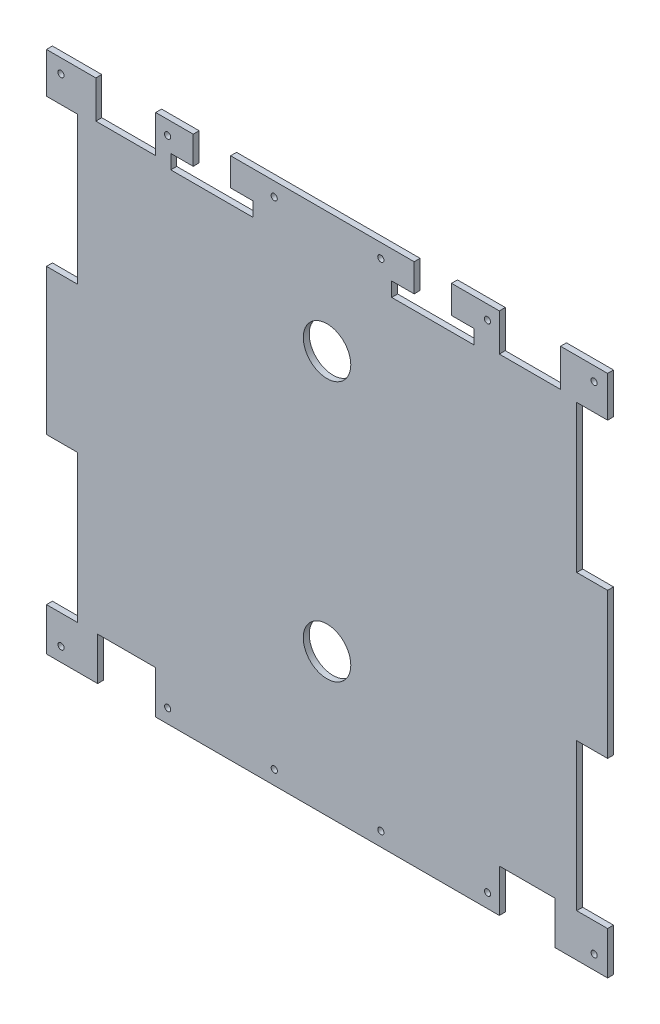
SolidWorks part; units mm, degrees
material "PBT General Purpose"
ref_plane "Front" through (0, 0, 0) normal (0, 0, 1) x (1, 0, 0)
ref_plane "Top" through (0, 0, 0) normal (0, 1, 0) x (1, 0, 0)
ref_plane "Right" through (0, 0, 0) normal (1, 0, 0) x (0, 0, -1)
sketch "Sketch5" plane through (0, 0, 0) normal (0, 0, 1) x (1, 0, 0)
  line L0 (47.1246, -7.4523) -> (30.6146, -7.4523)
  line L1 (-252.8494, 249.5587) -> (-226.474, 249.5587)
  line L2 (-252.8494, 249.5587) -> (-252.8494, 227.8859)
  line L3 (-252.8494, -30.3493) -> (-225.4703, -30.3493)
  line L4 (47.1246, 249.5587) -> (47.1246, 227.8859)
  line L5 (30.6146, -7.4523) -> (30.6146, 71.2877)
  line L6 (30.6146, 71.2877) -> (47.1246, 71.2877)
  line L8 (47.1246, -7.4523) -> (47.1246, -30.3493)
  line L9 (47.1246, 149.1459) -> (30.6146, 149.1459)
  line L10 (30.6146, 149.1459) -> (30.6146, 227.8859)
  line L11 (30.6146, 227.8859) -> (47.1246, 227.8859)
  line L13 (47.1246, 149.1459) -> (47.1246, 71.2877)
  line L14 (-252.8494, 227.8859) -> (-236.3394, 227.8859)
  line L15 (-236.3394, 227.8859) -> (-236.3394, 149.1459)
  line L16 (-236.3394, 149.1459) -> (-252.8494, 149.1459)
  line L18 (-252.8494, 149.1459) -> (-252.8494, 71.2877)
  line L19 (-252.8494, 71.2877) -> (-236.3394, 71.2877)
  line L20 (-236.3394, 71.2877) -> (-236.3394, -7.4523)
  line L21 (-236.3394, -7.4523) -> (-252.8494, -7.4523)
  line L23 (-252.8494, -7.4523) -> (-252.8494, -30.3493)
  line L24 (47.1246, -22.8907) -> (-72.4065, -22.8907) construction
  line L25 (-252.8494, 242.1016) -> (-174.4024, 242.1016) construction
  line L26 (-75.7065, -22.8907) -> (-252.8494, -22.8907) construction
  line L27 (-56.3024, 249.5587) -> (-56.3024, 234.6507)
  line L28 (-56.3024, 227.0307) -> (-36.3024, 227.0307)
  line L29 (-36.3024, 234.6507) -> (-36.3024, 249.5587)
  line L31 (-174.4024, 249.5587) -> (-174.4024, 234.6507)
  line L32 (-174.4024, 227.0307) -> (-154.4024, 227.0307)
  line L33 (-154.4024, 234.6507) -> (-154.4024, 249.5587)
  line L35 (-154.4024, 249.5587) -> (-56.3024, 249.5587)
  line L36 (-154.4024, 242.1016) -> (-56.3024, 242.1016) construction
  line L37 (-36.3024, 249.5587) -> (-10.756, 249.5587)
  line L38 (-36.3024, 242.1016) -> (47.1246, 242.1016) construction
  line L39 (-36.3024, 234.6507) -> (-24.3024, 234.6507)
  line L40 (-252.8494, 234.6507) -> (47.1506, 234.6507) construction
  line L41 (-24.3024, 234.6507) -> (-24.3024, 227.0307)
  line L42 (-24.3024, 227.0307) -> (-36.3024, 227.0307)
  line L43 (-56.3024, 234.6507) -> (-68.3024, 234.6507)
  line L44 (-174.4024, 234.6507) -> (-186.4024, 234.6507)
  line L45 (-54.6336, 234.6507) -> (-154.6336, 234.6507) construction
  line L46 (-68.3024, 234.6507) -> (-68.3024, 227.0307)
  line L47 (-68.3024, 227.0307) -> (-56.3024, 227.0307)
  line L48 (-186.4024, 234.6507) -> (-186.4024, 227.0307)
  line L49 (-186.4024, 227.0307) -> (-174.4024, 227.0307)
  line L50 (-154.4024, 234.6507) -> (-142.4024, 234.6507)
  line L51 (-142.4024, 234.6507) -> (-142.4024, 227.0307)
  line L52 (-142.4024, 227.0307) -> (-154.4024, 227.0307)
  line L53 (-194.456, 249.5587) -> (-174.4024, 249.5587)
  line L55 (-10.756, 249.5587) -> (-10.756, 229.5587)
  line L56 (-10.756, 229.5587) -> (21.9637, 229.5587)
  line L57 (21.9637, 249.5587) -> (21.9637, 229.5587)
  line L59 (-226.474, 249.5587) -> (-226.474, 229.5587)
  line L60 (-226.474, 229.5587) -> (-194.456, 229.5587)
  line L61 (-194.456, 249.5587) -> (-194.456, 229.5587)
  line L62 (21.9637, 249.5587) -> (47.1246, 249.5587)
  line L63 (-194.456, -30.3493) -> (-10.756, -30.3493)
  line L64 (-225.4703, -7.4522) -> (-194.456, -7.4522)
  line L65 (-225.4703, -7.4522) -> (-225.4703, -30.3493)
  line L67 (-194.456, -7.4522) -> (-194.456, -30.3493)
  line L68 (18.9189, -7.4522) -> (-10.756, -7.4522)
  line L69 (18.9189, -7.4522) -> (18.9189, -30.3493)
  line L71 (-10.756, -7.4522) -> (-10.756, -30.3493)
  line L72 (18.9189, -30.3493) -> (47.1246, -30.3493)
  circle A8 centre (39.9435, -22.8907) radius 1.65
  circle A10 centre (-17.0565, -22.8907) radius 1.65
  circle A11 centre (-74.0565, -22.8907) radius 1.65
  circle A12 centre (-131.0565, -22.8907) radius 1.65
  circle A13 centre (-188.0565, -22.8907) radius 1.65
  circle A14 centre (-245.0565, -22.8907) radius 1.65
  circle A15 centre (39.894, 242.1016) radius 1.65
  circle A16 centre (-17.106, 242.1016) radius 1.65
  circle A17 centre (-74.106, 242.1016) radius 1.65
  circle A18 centre (-131.106, 242.1016) radius 1.65
  circle A19 centre (-188.106, 242.1016) radius 1.65
  circle A20 centre (-245.106, 242.1016) radius 1.65
  circle A22 centre (-102.8624, 184.8543) radius 12.7
  circle A23 centre (-102.8624, 45.8507) radius 12.7
  point P12 (38.8696, 149.1459)
  point P99 (-271.9767, 260.7641)
  dimension "D10" = 3.3
  dimension "D12" = 3.3
  dimension "D14" = 25.4
  dimension "D15" = 25.4
  dimension "D1" = 299.974
  dimension "D2" = 279.908
  dimension "D3" = 16.51
  dimension "D4" = 16.51
  dimension "D5" = 16.51
  dimension "D6" = 78.74
  dimension "D7" = 78.74
  dimension "D8" = 78.74
  dimension "D9" = 16.51
  dimension "D16" = 76.2
  dimension "D17" = 20
  dimension "D18" = 7.62
  dimension "D19" = 12
  dimension "D20" = 12
  dimension "D21" = 12
  dimension "D22" = 12
  dimension "D23" = 6.35
  dimension "D24" = 279.908
  dimension "D25" = 7.62
  dimension "D26" = 6.35
  dimension "D11" = 6
  dimension "D13" = 6
extrude "Boss-Extrude1" add sketch "Sketch5" along normal blind 3.175
